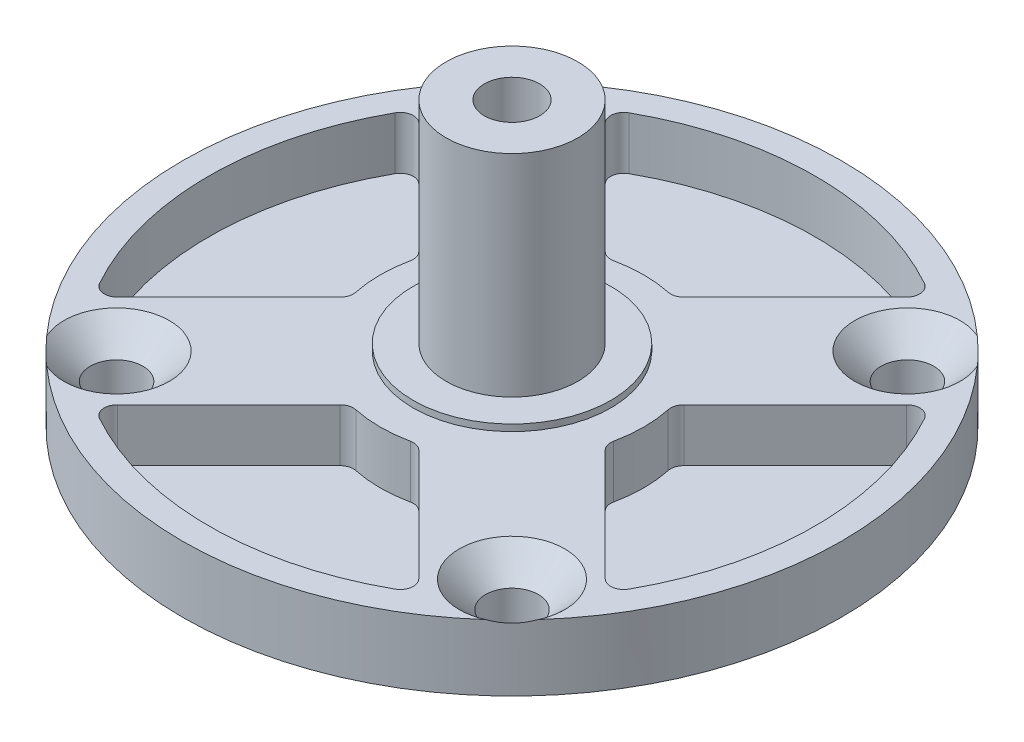
SolidWorks part; units mm, degrees
material "AISI 304"
ref_plane "前视基准面" through (0, 0, 0) normal (0, 0, 1) x (1, 0, 0)
ref_plane "上视基准面" through (0, 0, 0) normal (0, 1, 0) x (1, 0, 0)
ref_plane "右视基准面" through (0, 0, 0) normal (1, 0, 0) x (0, 0, -1)
sketch "草图1" plane through (0, 0, 0) normal (0, 1, 0) x (1, 0, 0)
  circle A0 centre (0, 0) radius 25
  dimension "D1" = 50
extrude "凸台-拉伸1" add sketch "草图1" along normal blind 5
sketch "草图2" plane through (0, 5, 0) normal (0, 1, 0) x (1, 0, 0)
  circle A0 centre (0, 0) radius 17.5 construction
  circle A1 centre (0, 17.5) radius 2.05
  dimension "D1" = 35
  dimension "D2" = 4.1
extrude "切除-拉伸1" [suppressed] cut sketch "草图2" against normal through all
pattern_circular "阵列(圆周)1" [suppressed] count 4 over 360 of bodies 107
sketch "草图3" plane through (0, 5, 0) normal (0, 1, 0) x (1, 0, 0)
  circle A0 centre (0, 0) radius 7.5
  dimension "D1" = 15
extrude "凸台-拉伸2" add sketch "草图3" along normal blind 0.5
sketch "草图4" plane through (0, 5.5, 0) normal (0, 1, 0) x (1, 0, 0)
  circle A0 centre (0, 0) radius 5
  dimension "D1" = 10
extrude "凸台-拉伸3" add sketch "草图4" along normal blind 16
sketch "草图8" plane through (0, 0, 0) normal (0, -1, 0) x (-1, 0, 0)
  line L1 (-15, -15) -> (15, -15) construction
  line L2 (-15, -15) -> (-15, 15) construction
  line L3 (-15, 15) -> (15, 15) construction
  line L4 (15, -15) -> (15, 15) construction
  circle A0 centre (0, 0) radius 25 construction
  circle A1 centre (-15, -15) radius 2
  circle A2 centre (15, -15) radius 2
  circle A3 centre (15, 15) radius 2
  circle A4 centre (-15, 15) radius 2
  dimension "D3" = 15
  dimension "D4" = 4
  dimension "D1" = 30
  dimension "D2" = 15
extrude "切除-拉伸2" cut sketch "草图8" against normal through all
chamfer "倒角1" distance 2 angle 45 4 edges at (-15, 5, -13) (-15, 5, 17) (15, 5, -13) (15, 5, 17)
sketch "草图13" plane through (0, 5, 0) normal (0, 1, 0) x (1, 0, 0)
  line L0 (0, -25.5) -> (0, 0) construction
  line L1 (-12.339, 19.41) -> (-2.5882, 9.6593)
  line L2 (12.339, 19.41) -> (2.5882, 9.6593)
  line L3 (19.41, -12.339) -> (9.6593, -2.5882)
  line L4 (19.41, 12.339) -> (9.6593, 2.5882)
  line L5 (-12.339, -19.41) -> (-2.5882, -9.6593)
  line L6 (12.339, -19.41) -> (2.5882, -9.6593)
  line L7 (-19.41, 12.339) -> (-9.6593, 2.5882)
  line L8 (-19.41, -12.339) -> (-9.6593, -2.5882)
  arc A0 (-12.339, 19.41) -> (12.339, 19.41) centre (0, 0) cw
  circle A1 centre (0, 0) radius 25 construction
  arc A2 (-2.5882, 9.6593) -> (2.5882, 9.6593) centre (0, 0) cw
  arc A3 (9.6593, 2.5882) -> (9.6593, -2.5882) centre (0, 0) cw
  arc A4 (19.41, 12.339) -> (19.41, -12.339) centre (0, 0) cw
  arc A5 (2.5882, -9.6593) -> (-2.5882, -9.6593) centre (0, 0) cw
  arc A6 (12.339, -19.41) -> (-12.339, -19.41) centre (0, 0) cw
  arc A7 (-9.6593, -2.5882) -> (-9.6593, 2.5882) centre (0, 0) cw
  arc A8 (-19.41, -12.339) -> (-19.41, 12.339) centre (0, 0) cw
  dimension "D1" = 10
  dimension "D2" = 23
  dimension "D4" = 10
  dimension "D3" = 4
extrude "切除-拉伸5" cut sketch "草图13" against normal blind 4
fillet "圆角1" radius 1 16 edges at (19.41, 3, -12.339) (9.6593, 3, -2.5882) (9.6593, 3, 2.5882) (19.41, 3, 12.339) (12.339, 3, 19.41) (2.5882, 3, 9.6593) (-2.5882, 3, 9.6593) (-12.339, 3, 19.41) (-19.41, 3, 12.339) (-19.41, 3, -12.339) (-9.6593, 3, 2.5882) (-9.6593, 3, -2.5882) (12.339, 3, -19.41) (2.5882, 3, -9.6593) (-2.5882, 3, -9.6593) (-12.339, 3, -19.41)
hole_wizard "M5 螺纹孔1" positions "草图14" profile "草图15" tap size "M5" standard "GB"
sketch "草图14" plane through (0, 21.5, 0) normal (0, 1, 0) x (1, 0, 0)
  point P0 (0, 0)
sketch "草图15" plane through (0, 21.5, 0) normal (1, 0, 0) x (0, 0, 1)
  line L0 (0, 0) -> (0, 13.6618)
  line L1 (0, 13.6618) -> (2.1, 12.4)
  line L2 (2.1, 12.4) -> (2.1, 0)
  line L5 (2.1, 0) -> (0, 0)
  line L10 (0, 13.6618) -> (-2.1, 12.4) construction
  line L11 (0, -6.35) -> (0, 107.95) construction
  dimension "螺纹孔钻头直径" = 4.2
  dimension "螺纹孔钻头深度" = 12.4
  dimension "导头角度" = 118
cosmetic thread "孔螺蚊线2" parameters "D1"=10, "D2"=5
